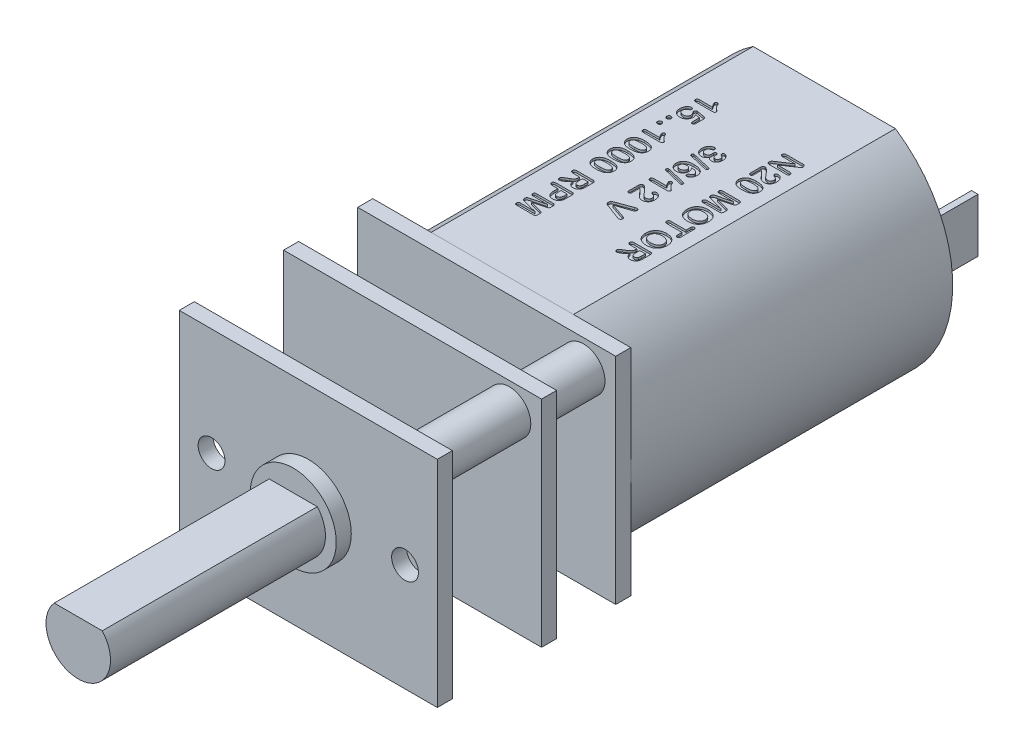
SolidWorks part; units mm, degrees
ref_plane "Front Plane" through (0, 0, 0) normal (0, 0, 1) x (1, 0, 0)
ref_plane "Top Plane" through (0, 0, 0) normal (0, 1, 0) x (1, 0, 0)
ref_plane "Right Plane" through (0, 0, 0) normal (1, 0, 0) x (0, 0, -1)
sketch "Sketch1" plane through (0, 0, 0) normal (0, 0, 1) x (1, 0, 0)
  line L0 (-6, 0) -> (6, 0) construction
  line L1 (-6, -5) -> (6, -5)
  line L2 (-6, -5) -> (-6, 5)
  line L3 (-6, 5) -> (6, 5)
  line L4 (6, -5) -> (6, 5)
  line L5 (-6, -5) -> (6, 5) construction
  line L6 (-6, 5) -> (6, -5) construction
  line L7 (-1.118, 1) -> (1.118, 1)
  line L8 (0, 5) -> (0, -5) construction
  line L9 (-3.3091, 4.975) -> (3.3091, 4.975)
  line L10 (-3.3091, -4.975) -> (3.3091, -4.975)
  line L11 (-4, 1.25) -> (-4, -1.25) construction
  line L12 (3.85, 1.25) -> (4.15, 1.25)
  line L13 (3.85, 1.25) -> (3.85, -1.25)
  line L14 (3.85, -1.25) -> (4.15, -1.25)
  line L15 (4.15, 1.25) -> (4.15, -1.25)
  line L16 (3.85, 1.25) -> (4.15, -1.25) construction
  line L17 (3.85, -1.25) -> (4.15, 1.25) construction
  line L18 (-4.15, 1.25) -> (-3.85, 1.25)
  line L19 (-4.15, 1.25) -> (-4.15, -1.25)
  line L20 (-4.15, -1.25) -> (-3.85, -1.25)
  line L21 (-3.85, 1.25) -> (-3.85, -1.25)
  line L22 (-4.15, 1.25) -> (-3.85, -1.25) construction
  line L23 (-4.15, -1.25) -> (-3.85, 1.25) construction
  line L24 (4, 1.25) -> (4, -1.25) construction
  arc A0 (-1.118, 1) -> (1.118, 1) centre (0, 0) ccw
  circle A1 centre (0, 0) radius 2
  circle A2 centre (-4.5, 0) radius 0.5
  circle A3 centre (4.5, 0) radius 0.5
  circle A4 centre (-4.5, -3.75) radius 1
  circle A5 centre (4.5, 3.75) radius 1
  arc A6 (3.3091, -4.975) -> (3.3091, 4.975) centre (0, 0) ccw
  arc A7 (-3.3091, 4.975) -> (-3.3091, -4.975) centre (0, 0) ccw
  circle A8 centre (0, 0) radius 2.5
  point P0 (0, 0)
  point P26 (4, 0)
  point P32 (-4, 0)
  dimension "D1" = 3
  dimension "D2" = 4
  dimension "D6" = 9
  dimension "D7" = 1
  dimension "D8" = 2
  dimension "D9" = 9
  dimension "D11" = 11.95
  dimension "D13" = 5
  dimension "D3" = 12
  dimension "D4" = 10
  dimension "D5" = 1
  dimension "D10" = 4.5
  dimension "D12" = 9.95
  dimension "D14" = 0.3
  dimension "D15" = 2.5
  dimension "D16" = 8
extrude "Boss-Extrude1" add sketch "Sketch1" along normal blind 0.7 contours A1
extrude "Boss-Extrude2" add sketch "Sketch1<3>" along normal blind 10.7 contours A0 L7
sketch "Sketch1<3>" plane through (0, 0, 0) normal (0, 0, 1) x (1, 0, 0) same geometry as "Sketch1"
extrude "Boss-Extrude3" add sketch "Sketch1<5>" against normal blind 0.7 contours L4 L3 L2 L1
sketch "Sketch1<5>" plane through (0, 0, 0) normal (0, 0, 1) x (1, 0, 0) same geometry as "Sketch1"
extrude "Boss-Extrude4" add sketch "Sketch1<6>" against normal blind 0.7 from offset 4.85 separate body contours L3 L4 L1 L2 offset against normal yes
sketch "Sketch1<6>" plane through (0, 0, 0) normal (0, 0, 1) x (1, 0, 0) same geometry as "Sketch1"
extrude "Boss-Extrude5" add sketch "Sketch1<7>" against normal blind 0.7 from offset 8.3 separate body contours L3 L4 L1 L2 offset against normal yes
sketch "Sketch1<7>" plane through (0, 0, 0) normal (0, 0, 1) x (1, 0, 0) same geometry as "Sketch1"
extrude "Boss-Extrude6" add sketch "Sketch1<8>" against normal up to surface (9 mm away) contours A4 | A5 up to face at (0, 0, -9)
sketch "Sketch1<8>" plane through (0, 0, 0) normal (0, 0, 1) x (1, 0, 0) same geometry as "Sketch1"
extrude "Boss-Extrude7" add sketch "Sketch1<9>" against normal blind 15 from surface contours A6 L9 A7 L10 starting at face at (0, 0, -9)
sketch "Sketch1<9>" plane through (0, 0, 0) normal (0, 0, 1) x (1, 0, 0) same geometry as "Sketch1"
extrude "Boss-Extrude8" add sketch "Sketch1<10>" against normal blind 0.7 from surface contours A8 starting at face at (0, 0, -24)
sketch "Sketch1<10>" plane through (0, 0, 0) normal (0, 0, 1) x (1, 0, 0) same geometry as "Sketch1"
extrude "Boss-Extrude9" add sketch "Sketch1<11>" against normal blind 3 from surface contours L15 L14 L13 L12 | L21 L20 L19 L18 starting at face at (-2.5, 0, -24)
sketch "Sketch1<11>" plane through (0, 0, 0) normal (0, 0, 1) x (1, 0, 0) same geometry as "Sketch1"
sketch "Sketch2" plane through (0, 4.975, 0) normal (0, 1, 0) x (1, 0, 0)
  line L0 (1.7257, 24) -> (1.7257, 9) construction
  line L1 (3.3091, 24) -> (-3.3091, 24) construction
  line L2 (3.3091, 9) -> (-3.3091, 9) construction
  text T0 "N20 MOTOR\r\n3/6/12 V\r\n15..1000 RPM" font "Arial Rounded MT Bold" height 1
extrude "Cut-Extrude1" cut sketch "Sketch2" against normal blind 0.1
hole_wizard "M1.6 Tapped Hole1" positions "Sketch3" profile "Sketch4" tap size "M1.6" standard "DIN" end condition up to next
sketch "Sketch3" plane through (0, 0, 0) normal (0, 0, 1) x (1, 0, 0)
  point P0 (4.5, 0)
  point P2 (-4.5, 0)
sketch "Sketch4" plane through (4.5, 0, 0) normal (1, 0, 0) x (0, -1, 0)
  line L0 (0, 0) -> (0, 0.7)
  line L1 (0, 0.7) -> (0.625, 0.7)
  line L2 (0.625, 0.7) -> (0.625, 0)
  line L5 (0.625, 0) -> (0, 0)
  line L11 (0, -6.35) -> (0, 107.95) construction
  dimension "Thru Tap Drill Dia." = 1.25
  dimension "Thru Tap Drill Depth" = 0.7
cosmetic thread "Hole Thread1" parameters "D2"=1.6
cosmetic thread "Hole Thread2" parameters "D2"=1.6
